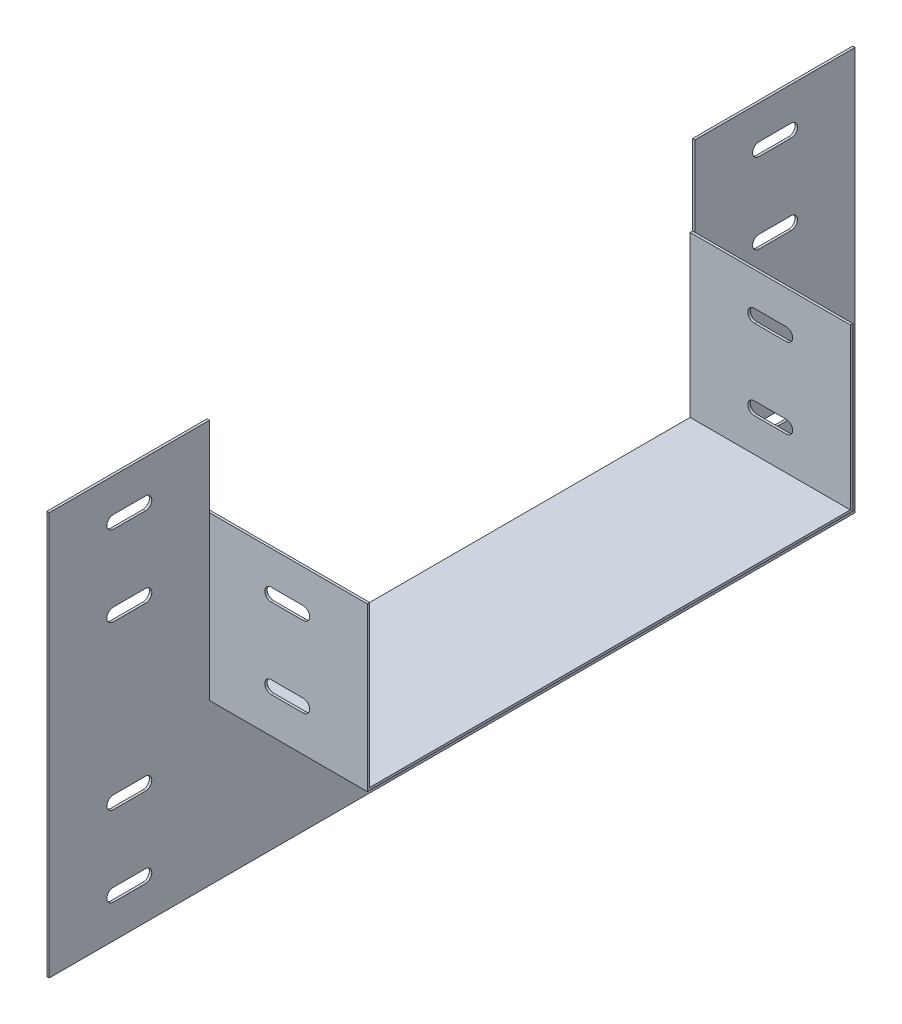
SolidWorks part; units mm, degrees
ref_plane "Front Plane" through (0, 0, 0) normal (0, 0, 1) x (1, 0, 0)
ref_plane "Top Plane" through (0, 0, 0) normal (0, 1, 0) x (1, 0, 0)
ref_plane "Right Plane" through (0, 0, 0) normal (1, 0, 0) x (0, 0, -1)
sketch "Sketch1" plane through (0, 0, 0) normal (0, 1, 0) x (1, 0, 0)
  line L2 (100, 150) -> (100, -150)
  line L3 (0, 150) -> (0, -150)
  line L5 (100, -150) -> (0, -150)
  line L11 (100, 150) -> (0, 150)
  dimension "Width" = 300
  dimension "Length" = 100
extrude "Boss-Extrude1" add sketch "Sketch1" against normal blind 1.5
sketch "Sketch2" plane through (0, 0, 0) normal (0, 1, 0) x (1, 0, 0)
  line L2 (0, -150) -> (100, -150) construction
  line L3 (0, -150) -> (100, -150)
  line L4 (100, 150) -> (0, 150) construction
  line L6 (100, 150) -> (0, 150)
extrude "Extrude-Thin1" add sketch "Sketch2" along normal blind 100 and the other way up to surface (1.5 mm away) thin other way up to face at (50, -1.5, 0) thin type one direction wall 1.5
sketch "Sketch3" plane through (0, 0, 0) normal (1, 0, 0) x (0, 0, -1)
  line L0 (-151.5, 150) -> (-151.5, -1.5)
  line L1 (-151.5, -1.5) -> (-151.5, 100) construction
  line L2 (151.5, 150) -> (151.5, -1.5)
  line L3 (-151.5, 150) -> (-251.5, 150)
  line L4 (-251.5, 150) -> (-251.5, -101.5)
  line L5 (-251.5, -101.5) -> (251.5, -101.5)
  line L6 (251.5, -101.5) -> (251.5, 150)
  line L7 (251.5, 150) -> (151.5, 150)
  line L8 (151.5, -1.5) -> (-151.5, -1.5)
  dimension "D1" = 100
  dimension "D2" = 100
  dimension "D3" = 50
extrude "Boss-Extrude2" add sketch "Sketch3" along normal blind 1.5
sketch "Sketch4" plane through (0, 0, 0) normal (0, 0, 1) x (1, 0, 0)
  line L0 (40, 75) -> (60, 75) construction
  line L1 (40, 79) -> (60, 79)
  line L2 (40, 71) -> (60, 71)
  line L3 (40, 25) -> (60, 25) construction
  line L4 (40, 29) -> (60, 29)
  line L5 (40, 21) -> (60, 21)
  line L6 (0, 50) -> (100, 50) construction
  line L9 (50, 0) -> (50, 50) construction
  line L10 (100, -1.5) -> (100, 100) construction
  line L11 (50, 50) -> (50, 100) construction
  arc A0 (40, 79) -> (40, 71) centre (40, 75) ccw
  arc A1 (60, 71) -> (60, 79) centre (60, 75) ccw
  arc A2 (40, 29) -> (40, 21) centre (40, 25) ccw
  arc A3 (60, 21) -> (60, 29) centre (60, 25) ccw
  point P2 (50, 75)
  point P8 (50, 25)
  dimension "D1" = 4
  dimension "D2" = 20
  dimension "D4" = 50
  dimension "D5" = 100
  dimension "D3" = 50
extrude "Cut-Extrude1" cut sketch "Sketch4" against normal through all and the other way through all
sketch "Sketch5" plane through (1.5, 0, 0) normal (1, 0, 0) x (0, 0, -1)
  line L0 (-251.5, 100) -> (-151.5, 100) construction
  line L2 (-251.5, 150) -> (-251.5, -101.5) construction
  line L3 (-201.5, 150) -> (-201.5, 100) construction
  line L4 (-151.5, 150) -> (-251.5, 150) construction
  line L5 (-201.5, 100) -> (-201.5, 50) construction
  line L6 (-251.5, -51.5) -> (-151.5, -51.5) construction
  line L7 (-211.5, 125) -> (-191.5, 125) construction
  line L8 (-211.5, 129) -> (-191.5, 129)
  line L9 (-211.5, 121) -> (-191.5, 121)
  line L10 (-211.5, 75) -> (-191.5, 75) construction
  line L11 (-211.5, 79) -> (-191.5, 79)
  line L12 (-211.5, 71) -> (-191.5, 71)
  line L13 (-201.5, -1.5) -> (-201.5, -51.5) construction
  line L14 (-201.5, -51.5) -> (-201.5, -101.5) construction
  line L15 (-211.5, -26.5) -> (-191.5, -26.5) construction
  line L16 (-211.5, -22.5) -> (-191.5, -22.5)
  line L17 (-211.5, -30.5) -> (-191.5, -30.5)
  line L18 (-211.5, -76.5) -> (-191.5, -76.5) construction
  line L19 (-211.5, -72.5) -> (-191.5, -72.5)
  line L20 (-211.5, -80.5) -> (-191.5, -80.5)
  line L21 (151.5, 100) -> (251.5, 100) construction
  line L22 (201.5, 150) -> (201.5, 100) construction
  line L23 (201.5, 100) -> (201.5, 50) construction
  line L24 (191.5, 125) -> (211.5, 125) construction
  line L25 (191.5, 129) -> (211.5, 129)
  line L26 (191.5, 121) -> (211.5, 121)
  line L27 (191.5, 75) -> (211.5, 75) construction
  line L28 (191.5, 79) -> (211.5, 79)
  line L29 (191.5, 71) -> (211.5, 71)
  line L30 (151.5, -51.5) -> (251.5, -51.5) construction
  line L31 (201.5, -1.5) -> (201.5, -51.5) construction
  line L32 (201.5, -51.5) -> (201.5, -101.5) construction
  line L33 (191.5, -26.5) -> (211.5, -26.5) construction
  line L34 (191.5, -22.5) -> (211.5, -22.5)
  line L35 (191.5, -30.5) -> (211.5, -30.5)
  line L36 (191.5, -76.5) -> (211.5, -76.5) construction
  line L37 (191.5, -72.5) -> (211.5, -72.5)
  line L38 (191.5, -80.5) -> (211.5, -80.5)
  line L39 (251.5, -101.5) -> (251.5, 150) construction
  line L40 (251.5, 150) -> (151.5, 150) construction
  line L41 (-251.5, -101.5) -> (251.5, -101.5) construction
  arc A0 (-211.5, 129) -> (-211.5, 121) centre (-211.5, 125) ccw
  arc A1 (-191.5, 121) -> (-191.5, 129) centre (-191.5, 125) ccw
  arc A2 (-211.5, 79) -> (-211.5, 71) centre (-211.5, 75) ccw
  arc A3 (-191.5, 71) -> (-191.5, 79) centre (-191.5, 75) ccw
  arc A4 (-211.5, -22.5) -> (-211.5, -30.5) centre (-211.5, -26.5) ccw
  arc A5 (-191.5, -30.5) -> (-191.5, -22.5) centre (-191.5, -26.5) ccw
  arc A6 (-211.5, -72.5) -> (-211.5, -80.5) centre (-211.5, -76.5) ccw
  arc A7 (-191.5, -80.5) -> (-191.5, -72.5) centre (-191.5, -76.5) ccw
  arc A8 (191.5, 129) -> (191.5, 121) centre (191.5, 125) ccw
  arc A9 (211.5, 121) -> (211.5, 129) centre (211.5, 125) ccw
  arc A10 (191.5, 79) -> (191.5, 71) centre (191.5, 75) ccw
  arc A11 (211.5, 71) -> (211.5, 79) centre (211.5, 75) ccw
  arc A12 (191.5, -22.5) -> (191.5, -30.5) centre (191.5, -26.5) ccw
  arc A13 (211.5, -30.5) -> (211.5, -22.5) centre (211.5, -26.5) ccw
  arc A14 (191.5, -72.5) -> (191.5, -80.5) centre (191.5, -76.5) ccw
  arc A15 (211.5, -80.5) -> (211.5, -72.5) centre (211.5, -76.5) ccw
  point P15 (-201.5, 125)
  point P21 (-201.5, 75)
  point P32 (-201.5, -26.5)
  point P38 (-201.5, -76.5)
  point P51 (201.5, 125)
  point P57 (201.5, 75)
  point P70 (201.5, -26.5)
  point P76 (201.5, -76.5)
  dimension "D1" = 4
  dimension "D2" = 20
  dimension "D4" = 50
  dimension "D5" = 100
extrude "Cut-Extrude2" cut sketch "Sketch5" against normal through all
sketch "Sketch6" plane through (0, 0, 0) normal (0, 1, 0) x (1, 0, 0)
  line L1 (100, -150) -> (100, 150) construction
  point P1 (100, 0)
  point P10 (0, 0)
other "CPoint1" parameters "Diameter"=10, "StubLength"=300
ref_axis "Axis1" through (110, 0, 0) along (-1, 0, 0)
other "RPoint1"
equation "\"D5@Extrude-Thin1\"=\"Thickness@Boss-Extrude1\""
equation "\"D3@Sketch4\"=\"Height@Extrude-Thin1\"/2"
equation "\"D4@Sketch4\"=\"Height@Extrude-Thin1\"/2"
equation "\"D4@Sketch5\"=\"Height@Extrude-Thin1\"/2"
equation "\"D1@Boss-Extrude2\"=\"Thickness@Boss-Extrude1\""
